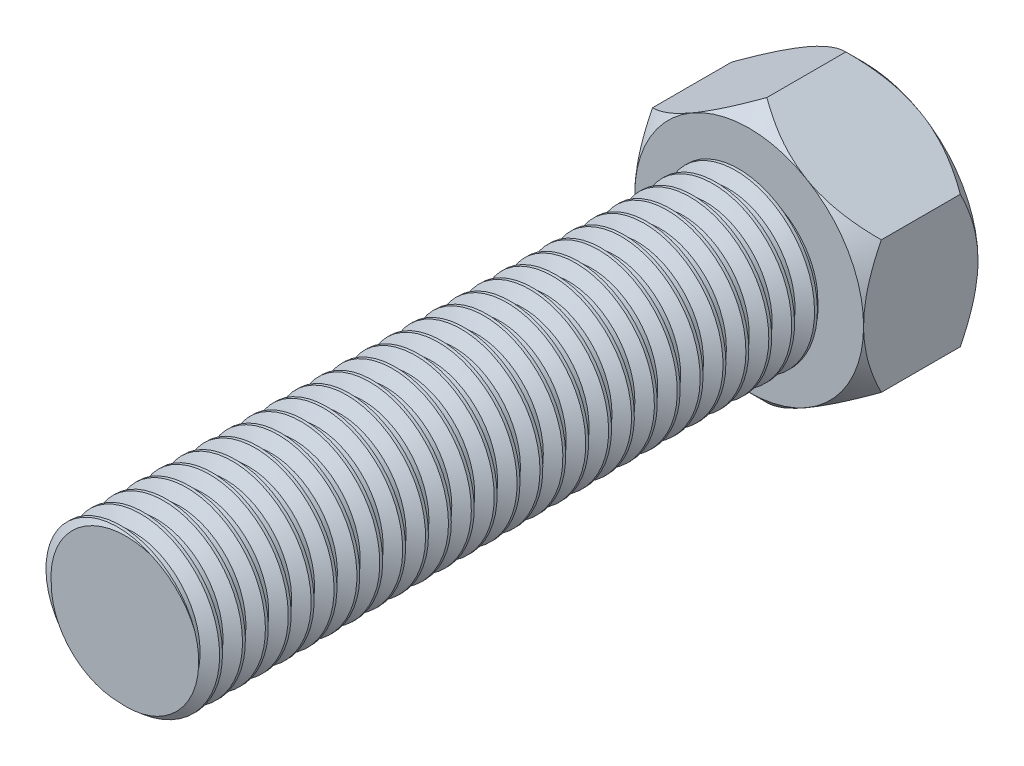
SolidWorks part; units mm, degrees
ref_plane "Front Plane" through (0, 0, 0) normal (0, 0, 1) x (1, 0, 0)
ref_plane "Top Plane" through (0, 0, 0) normal (0, 1, 0) x (1, 0, 0)
ref_plane "Right Plane" through (0, 0, 0) normal (1, 0, 0) x (0, 0, -1)
sketch "Sketch1" plane through (0, 0, 0) normal (0, 0, 1) x (1, 0, 0)
  line L1 (0, -5.7735) -> (5, -2.8868)
  line L2 (5, -2.8868) -> (5, 2.8868)
  line L3 (5, 2.8868) -> (0, 5.7735)
  line L4 (0, 5.7735) -> (-5, 2.8868)
  line L5 (-5, 2.8868) -> (-5, -2.8868)
  line L6 (-5, -2.8868) -> (0, -5.7735)
  circle A0 centre (0, 0) radius 5 construction
  circle A1 centre (0, 0) radius 3
  dimension "D1" = 10
  dimension "D2" = 6
extrude "Boss-Extrude1" add sketch "Sketch1" along normal mid plane 5 contours L5 L6 L1 L2 L3 L4 A1 | A1
sketch "Sketch2" plane through (0, 0, 2.5) normal (0, 0, 1) x (1, 0, 0)
  circle A0 centre (0, 0) radius 3
  dimension "D1" = 6
extrude "Boss-Extrude2" add sketch "Sketch2" along normal blind 27.5
sketch "Sketch3" plane through (0, 0, 2.5) normal (0, 0, 1) x (1, 0, 0)
  circle A0 centre (0, 0) radius 5
  dimension "D1" = 10
extrude "Cut-Extrude1" cut sketch "Sketch3" against normal blind 27.5 draft 45 flip side to cut
mirror "Mirror1" about plane through (0, 0, 0) normal (0, 0, 1) of "Cut-Extrude1"
thread "Thread1" start angle 0, offset 1, length 0, pitch 1, diameter 6
ref_plane "Plane1" through (-3, 0, 31) normal (0, -1, 0) x (-1, 0, 0)
sketch "Thread Profile1" plane through (-3, 0, 31) normal (0, -1, 0) x (-1, 0, 0)
  line L0 (0, 0) -> (0, 1) construction
  line L1 (0, 0) -> (0.5413, 0.3125)
  line L2 (0.5413, 0.3125) -> (0.5413, 0.4375)
  line L3 (0.5413, 0.4375) -> (0, 0.75)
  line L4 (0.5413, 0.375) -> (0, 0.375) construction
  line L11 (0, 0) -> (0, 0.75)
  point P2 (0, 0)
  dimension "Pitch" = 1
  dimension "Profile_Angle" = 60
  dimension "Profile_Land" = 0.125
  dimension "Profile_Height" = 0.5413
